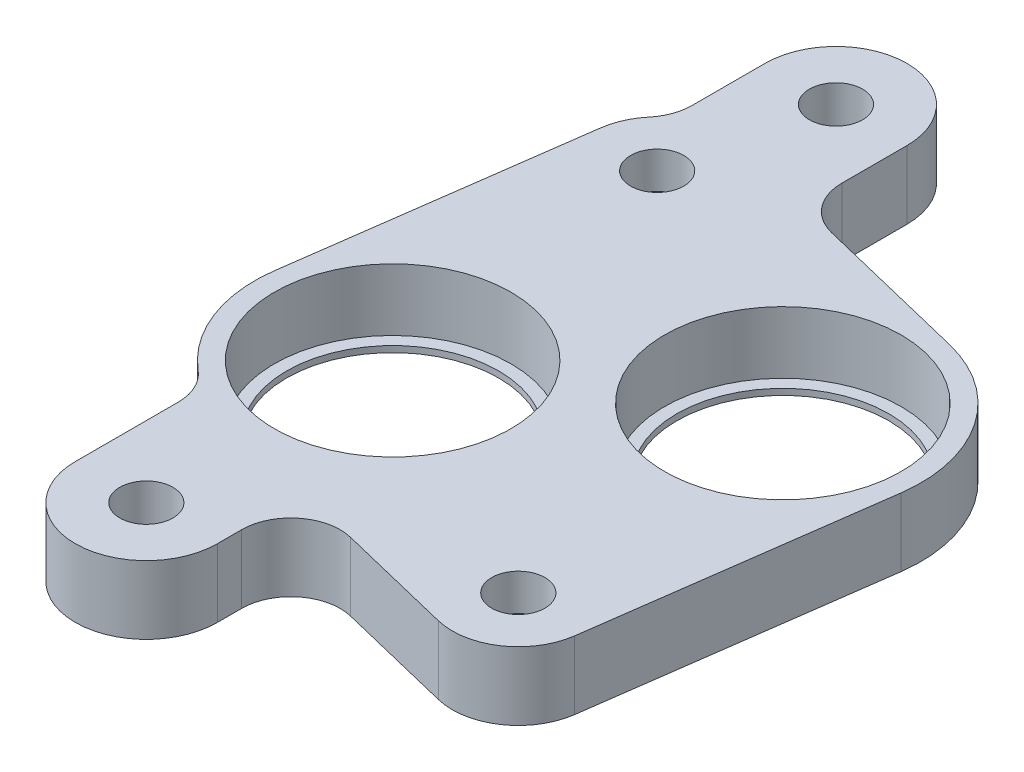
SolidWorks part; units mm, degrees
ref_plane "Front Plane" through (0, 0, 0) normal (0, 0, 1) x (1, 0, 0)
ref_plane "Top Plane" through (0, 0, 0) normal (0, 1, 0) x (1, 0, 0)
ref_plane "Right Plane" through (0, 0, 0) normal (1, 0, 0) x (0, 0, -1)
sketch "Sketch1" plane through (0, 0, 0) normal (0, -1, 0) x (-1, 0, 0)
  line L0 (-14.9625, 10.1854) -> (-17.0236, -8.9252) construction
  line L1 (-17.0236, -8.9252) -> (0, 0) construction
  line L2 (0, 0) -> (2.0611, 19.1106) construction
  line L3 (2.0611, 19.1106) -> (-14.9625, 10.1854) construction
  line L4 (-8.5895, 16.3936) -> (3.7867, 3.6887) construction
  line L5 (-8.5895, 16.3936) -> (-6.3152, 18.609) construction
  line L6 (-6.3152, 18.609) -> (6.061, 5.9042) construction
  line L7 (6.061, 5.9042) -> (3.7867, 3.6887) construction
  line L8 (7.627, 0) -> (8.897, 0) construction
  line L9 (3.7756, 19.1106) -> (6.3156, 19.1106) construction
  line L10 (-18.7381, -8.9252) -> (-21.2781, -8.9252) construction
  line L11 (-21.2385, -9.5041) -> (-23.7767, 8.9747)
  line L12 (-17.0682, 18.8296) -> (1.0542, 23.2442)
  line L13 (6.276, 19.6895) -> (8.8142, 1.2107)
  line L14 (-16.0167, -13.0588) -> (2.1057, -8.6442)
  circle A0 centre (-14.9625, 10.1854) radius 7.627
  circle A1 centre (0, 0) radius 7.627
  circle A3 centre (2.0611, 19.1106) radius 1.7145
  circle A4 centre (-17.0236, -8.9252) radius 1.7145
  circle A5 centre (-14.9625, 10.1854) radius 7.5 construction
  circle A6 centre (0, 0) radius 5.2864 construction
  circle A9 centre (-14.9625, 10.1854) radius 8.897 construction
  circle A10 centre (2.0611, 19.1106) radius 4.2545 construction
  circle A11 centre (0, 0) radius 8.897 construction
  circle A12 centre (-17.0236, -8.9252) radius 4.2545 construction
  arc A13 (-17.0682, 18.8296) -> (-23.7767, 8.9747) centre (-14.9625, 10.1854) ccw
  arc A14 (-21.2385, -9.5041) -> (-16.0167, -13.0588) centre (-17.0236, -8.9252) ccw
  arc A15 (8.8142, 1.2107) -> (2.1057, -8.6442) centre (0, 0) cw
  arc A16 (6.276, 19.6895) -> (1.0542, 23.2442) centre (2.0611, 19.1106) ccw
  point P16 (-14.9625, 10.1854)
  point P39 (-9.185, 16.9513)
  dimension "D1" = 0.127
  dimension "D2" = 3.429
  dimension "D3" = 3.175
  dimension "D4" = 6.35
  dimension "D6" = 2.54
  dimension "D5" = 1.27
extrude "Boss-Extrude1" add sketch "Sketch1" against normal up to surface (4 mm away)
sketch "Sketch2" plane through (0, 0, 0) normal (0, -1, 0) x (1, 0, 0)
  line L4 (16.0167, 13.0588) -> (-2.1057, 8.6442)
  line L5 (-8.8142, -1.2107) -> (-6.276, -19.6895)
  line L6 (-1.0542, -23.2442) -> (17.0682, -18.8296)
  line L7 (23.7767, -8.9747) -> (21.2385, 9.5041)
  line L8 (16.0167, 13.0588) -> (-2.1057, 8.6442)
  line L9 (-8.8142, -1.2107) -> (-6.276, -19.6895)
  line L10 (-1.0542, -23.2442) -> (17.0682, -18.8296)
  line L11 (23.7767, -8.9747) -> (21.2385, 9.5041)
  circle A0 centre (14.9625, -10.1854) radius 6.8332
  circle A1 centre (0, 0) radius 6.8332
  circle A2 centre (14.9625, -10.1854) radius 7.627 construction
  arc A4 (21.2385, 9.5041) -> (16.0167, 13.0588) centre (17.0236, 8.9252) ccw
  arc A5 (-2.1057, 8.6442) -> (-8.8142, -1.2107) centre (0, 0) ccw
  arc A6 (-6.276, -19.6895) -> (-1.0542, -23.2442) centre (-2.0611, -19.1106) ccw
  arc A7 (17.0682, -18.8296) -> (23.7767, -8.9747) centre (14.9625, -10.1854) ccw
  arc A8 (21.2385, 9.5041) -> (16.0167, 13.0588) centre (17.0236, 8.9252) ccw
  arc A9 (-2.1057, 8.6442) -> (-8.8142, -1.2107) centre (0, 0) ccw
  arc A10 (-6.276, -19.6895) -> (-1.0542, -23.2442) centre (-2.0611, -19.1106) ccw
  arc A11 (17.0682, -18.8296) -> (23.7767, -8.9747) centre (14.9625, -10.1854) ccw
  dimension "D2" = 0.7937
  dimension "D1" = 0
extrude "Boss-Extrude2" add sketch "Sketch2" along normal blind 0.3969
sketch "Sketch3" plane through (0, -0.3969, 0) normal (0, -1, 0) x (1, 0, 0)
  circle A0 centre (17.0236, 8.9252) radius 2.794
  circle A1 centre (-2.0611, -19.1106) radius 2.794
  dimension "D1" = 5.588
extrude "Cut-Extrude1" cut sketch "Sketch3" against normal blind 2.032
sketch "Sketch6" plane through (0, -0.3969, 0) normal (0, -1, 0) x (1, 0, 0)
  line L1 (-4.581, 7.627) -> (4.581, 7.627) construction
  line L2 (-4.581, 7.627) -> (-4.581, 15.875)
  line L4 (4.581, 7.627) -> (4.581, 15.875) construction
  line L6 (-4.581, -22.5385) -> (-4.581, -28.575)
  line L7 (-4.581, -28.575) -> (4.581, -28.575) construction
  line L8 (4.581, -21.8715) -> (4.581, -28.575)
  line L9 (16.0167, 13.0588) -> (-2.1057, 8.6442) construction
  line L10 (-2.1057, 8.6442) -> (4.581, 10.2731)
  line L11 (4.581, 10.2731) -> (4.581, 15.875)
  line L12 (-1.0542, -23.2442) -> (17.0682, -18.8296) construction
  line L13 (-1.0542, -23.2442) -> (4.581, -21.8715)
  arc A0 (-2.1057, 8.6442) -> (-8.8142, -1.2107) centre (0, 0) ccw construction
  circle A1 centre (0, 0) radius 7.627 construction
  arc A2 (4.581, 15.875) -> (-4.581, 15.875) centre (0, 15.875) ccw
  circle A3 centre (0, 15.875) radius 1.7145
  arc A4 (-4.581, -28.575) -> (4.581, -28.575) centre (0, -28.575) ccw
  circle A5 centre (0, -28.575) radius 1.7145
  arc A7 (-4.581, 7.627) -> (-2.1057, 8.6442) centre (0, 0) cw
  arc A8 (-6.276, -19.6895) -> (-1.0542, -23.2442) centre (-2.0611, -19.1106) ccw construction
  arc A9 (-1.0542, -23.2442) -> (-4.581, -22.5385) centre (-2.0611, -19.1106) cw
  point P7 (0, 7.627)
  dimension "D1" = 3.429
  dimension "D2" = 15.875
  dimension "D3" = 28.575
extrude "Boss-Extrude5" add sketch "Sketch6" against normal up to surface (4.3969 mm away) up to face at (7.4813, 4, -5.0927)
fillet "Fillet1" radius 3.175 4 edges at (4.581, 1.8016, 10.2731) (-4.581, 1.8016, 7.627) (4.581, 1.8016, -21.8715) (-4.581, 1.8016, -22.5385)
